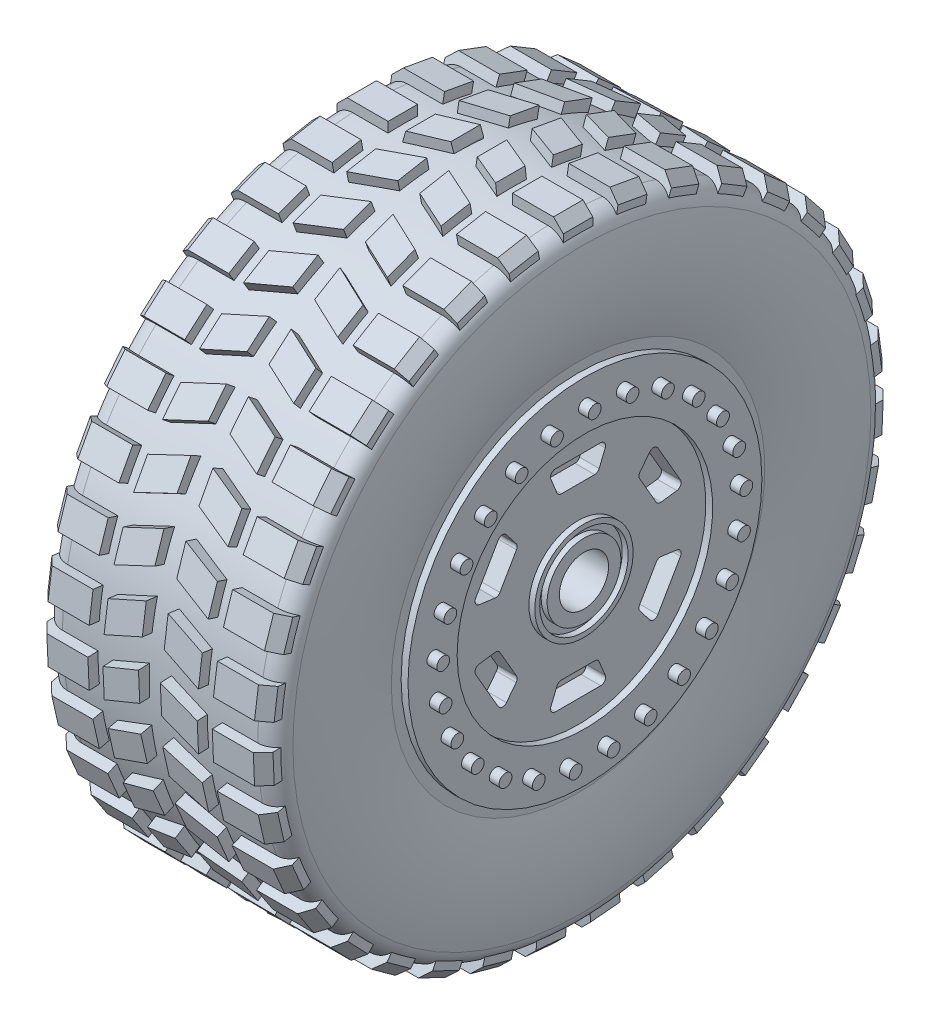
SolidWorks part; units mm, degrees
ref_plane "Front Plane" through (0, 0, 0) normal (0, 0, 1) x (1, 0, 0)
ref_plane "Top Plane" through (0, 0, 0) normal (0, 1, 0) x (1, 0, 0)
ref_plane "Right Plane" through (0, 0, 0) normal (1, 0, 0) x (0, 0, -1)
sketch "Sketch1" plane through (0, 0, 0) normal (0, 0, 1) x (1, 0, 0)
  line L0 (0, 0) -> (12.5125, 0) construction
  line L1 (0, 0) -> (0, 19)
  line L2 (0, 31) -> (11.5, 31)
  line L3 (11.5, 31) -> (11.5, 0)
  line L4 (11.5, 0) -> (0, 0)
  arc A0 (0, 19) -> (0, 31) centre (21.2241, 25) cw
  dimension "D1" = 19
  dimension "D2" = 31
  dimension "D3" = 11.5
revolve "Revolve1" add sketch "Sketch1" angle 360 about L0
sketch "Sketch2" plane through (0, 0, 0) normal (-1, 0, 0) x (0, 0, 1)
  circle A0 centre (0, 0) radius 18
  dimension "D1" = 36
extrude "Boss-Extrude1" add sketch "Sketch2" along normal blind 0.7
sketch "Sketch3" plane through (-0.7, 0, 0) normal (-1, 0, 0) x (0, 0, 1)
  circle A0 centre (0, 0) radius 13
  dimension "D1" = 26
extrude "Cut-Extrude1" cut sketch "Sketch3" against normal blind 0.7
sketch "Sketch4" plane through (0, 0, 0) normal (-1, 0, 0) x (0, 0, 1)
  line L0 (0, 0) -> (0, 8.2027) construction
  line L5 (1.6857, 8.2027) -> (-1.6857, 8.2027)
  line L6 (-2.1484, 8.5131) -> (-2.7624, 10.0114)
  line L7 (-2.2998, 10.701) -> (2.2998, 10.701)
  line L9 (2.1484, 8.5131) -> (2.7624, 10.0114)
  line L10 (0, 10.701) -> (0, 16.4054) construction
  line L11 (8.1174, 7.3422) -> (10.4172, 3.3588)
  line L12 (8.4467, 2.396) -> (10.0513, 2.6133)
  line L13 (7.9466, 2.6415) -> (6.2609, 5.5612)
  line L14 (6.2984, 6.1171) -> (7.2889, 7.398)
  line L15 (10.4172, -3.3588) -> (8.1174, -7.3422)
  line L16 (6.2984, -6.1171) -> (7.2889, -7.398)
  line L17 (6.2609, -5.5612) -> (7.9466, -2.6415)
  line L18 (8.4467, -2.396) -> (10.0513, -2.6133)
  line L19 (2.2998, -10.701) -> (-2.2998, -10.701)
  line L20 (-2.1484, -8.5131) -> (-2.7624, -10.0114)
  line L21 (-1.6857, -8.2027) -> (1.6857, -8.2027)
  line L22 (2.1484, -8.5131) -> (2.7624, -10.0114)
  line L23 (-8.1174, -7.3422) -> (-10.4172, -3.3588)
  line L24 (-8.4467, -2.396) -> (-10.0513, -2.6133)
  line L25 (-7.9466, -2.6415) -> (-6.2609, -5.5612)
  line L26 (-6.2984, -6.1171) -> (-7.2889, -7.398)
  line L27 (-10.4172, 3.3588) -> (-8.1174, 7.3422)
  line L28 (-6.2984, 6.1171) -> (-7.2889, 7.398)
  line L29 (-6.2609, 5.5612) -> (-7.9466, 2.6415)
  line L30 (-8.4467, 2.396) -> (-10.0513, 2.6133)
  arc A0 (2.7624, 10.0114) -> (2.2998, 10.701) centre (2.2998, 10.201) ccw
  arc A1 (2.1484, 8.5131) -> (1.6857, 8.2027) centre (1.6857, 8.7027) cw
  arc A2 (-1.6857, 8.2027) -> (-2.1484, 8.5131) centre (-1.6857, 8.7027) cw
  arc A3 (-2.7624, 10.0114) -> (-2.2998, 10.701) centre (-2.2998, 10.201) cw
  arc A4 (7.2889, 7.398) -> (8.1174, 7.3422) centre (7.6844, 7.0922) cw
  arc A5 (10.0513, 2.6133) -> (10.4172, 3.3588) centre (9.9842, 3.1088) ccw
  arc A6 (8.4467, 2.396) -> (7.9466, 2.6415) centre (8.3796, 2.8915) cw
  arc A7 (6.2609, 5.5612) -> (6.2984, 6.1171) centre (6.6939, 5.8112) cw
  arc A8 (10.0513, -2.6133) -> (10.4172, -3.3588) centre (9.9842, -3.1088) cw
  arc A9 (7.2889, -7.398) -> (8.1174, -7.3422) centre (7.6844, -7.0922) ccw
  arc A10 (6.2984, -6.1171) -> (6.2609, -5.5612) centre (6.6939, -5.8112) cw
  arc A11 (7.9466, -2.6415) -> (8.4467, -2.396) centre (8.3796, -2.8915) cw
  arc A12 (2.7624, -10.0114) -> (2.2998, -10.701) centre (2.2998, -10.201) cw
  arc A13 (-2.7624, -10.0114) -> (-2.2998, -10.701) centre (-2.2998, -10.201) ccw
  arc A14 (-2.1484, -8.5131) -> (-1.6857, -8.2027) centre (-1.6857, -8.7027) cw
  arc A15 (1.6857, -8.2027) -> (2.1484, -8.5131) centre (1.6857, -8.7027) cw
  arc A16 (-7.2889, -7.398) -> (-8.1174, -7.3422) centre (-7.6844, -7.0922) cw
  arc A17 (-10.0513, -2.6133) -> (-10.4172, -3.3588) centre (-9.9842, -3.1088) ccw
  arc A18 (-8.4467, -2.396) -> (-7.9466, -2.6415) centre (-8.3796, -2.8915) cw
  arc A19 (-6.2609, -5.5612) -> (-6.2984, -6.1171) centre (-6.6939, -5.8112) cw
  arc A20 (-10.0513, 2.6133) -> (-10.4172, 3.3588) centre (-9.9842, 3.1088) cw
  arc A21 (-7.2889, 7.398) -> (-8.1174, 7.3422) centre (-7.6844, 7.0922) ccw
  arc A22 (-6.2984, 6.1171) -> (-6.2609, 5.5612) centre (-6.6939, 5.8112) cw
  arc A23 (-7.9466, 2.6415) -> (-8.4467, 2.396) centre (-8.3796, 2.8915) cw
  point P12 (3.0451, 10.701)
  point P15 (2.0212, 8.2027)
  point P18 (-2.0212, 8.2027)
  point P21 (-3.0451, 10.701)
  point P83 (0, 0)
  dimension "D1" = 0.5
  dimension "D2" = 6
extrude "Cut-Extrude2" cut sketch "Sketch4" against normal blind 2
sketch "Sketch5" plane through (0, 0, 0) normal (-1, 0, 0) x (0, 0, 1)
  circle A0 centre (0, 0) radius 4.5
  circle A1 centre (0, 0) radius 5
  dimension "D1" = 10
  dimension "D2" = 9
extrude "Boss-Extrude2" add sketch "Sketch5" along normal blind 0.6
sketch "Sketch6" plane through (0, 0, 0) normal (-1, 0, 0) x (0, 0, 1)
  circle A0 centre (0, 0) radius 3.75
  dimension "D1" = 7.5
extrude "Boss-Extrude3" add sketch "Sketch6" along normal blind 0.6
sketch "Sketch7" plane through (-0.7, 0, 0) normal (-1, 0, 0) x (0, 0, 1)
  line L0 (0, 1.0659) -> (0, 26.7319) construction
  circle A0 centre (0, 15.4486) radius 0.65
  circle A1 centre (3.8419, 14.9633) radius 0.65
  circle A2 centre (7.4424, 13.5377) radius 0.65
  circle A3 centre (10.5753, 11.2615) radius 0.65
  circle A4 centre (13.0437, 8.2778) radius 0.65
  circle A5 centre (14.6925, 4.7739) radius 0.65
  circle A6 centre (15.4181, 0.97) radius 0.65
  circle A7 centre (15.175, -2.8948) radius 0.65
  circle A8 centre (13.9783, -6.5777) radius 0.65
  circle A9 centre (11.9034, -9.8473) radius 0.65
  circle A10 centre (9.0805, -12.4982) radius 0.65
  circle A11 centre (5.687, -14.3637) radius 0.65
  circle A12 centre (1.9362, -15.3268) radius 0.65
  circle A13 centre (-1.9362, -15.3268) radius 0.65
  circle A14 centre (-5.687, -14.3637) radius 0.65
  circle A15 centre (-9.0805, -12.4982) radius 0.65
  circle A16 centre (-11.9034, -9.8473) radius 0.65
  circle A17 centre (-13.9783, -6.5777) radius 0.65
  circle A18 centre (-15.175, -2.8948) radius 0.65
  circle A19 centre (-15.4181, 0.97) radius 0.65
  circle A20 centre (-14.6925, 4.7739) radius 0.65
  circle A21 centre (-13.0437, 8.2778) radius 0.65
  circle A22 centre (-10.5753, 11.2615) radius 0.65
  circle A23 centre (-7.4424, 13.5377) radius 0.65
  circle A24 centre (-3.8419, 14.9633) radius 0.65
  point P55 (0, 0)
  dimension "D1" = 1.3
  dimension "D2" = 25
extrude "Boss-Extrude4" add sketch "Sketch7" along normal blind 1
fillet "Fillet1" radius 2 1 edges at (0, 0, 31)
ref_plane "Plane1" through (0, 31, 0) normal (0, 1, 0) x (1, 0, 0)
sketch "Sketch8" plane through (0, 31, 0) normal (0, 1, 0) x (1, 0, 0)
  line L1 (0, -1.5) -> (5.1766, -1.5)
  line L2 (0, -1.5) -> (0, 1.5)
  line L3 (0, 1.5) -> (5.1766, 1.5)
  line L4 (5.1766, -1.5) -> (5.1766, 1.5)
  dimension "D1" = 1.5
  dimension "D2" = 3
extrude "Boss-Extrude5" add sketch "Sketch8" along normal blind 1 and the other way blind 1
chamfer "Chamfer1" distance 1 angle 45 1 edges at (0, 32, 0)
pattern_circular "CirPattern1" count 35 over 360 about axis through (0, 0, 0) along (1, 0, 0) of "Boss-Extrude5", "Chamfer1"
sketch "Sketch9" plane through (0, 31, 0) normal (0, 1, 0) x (1, 0, 0)
  line L0 (6.7047, -1.5491) -> (10.3876, 0)
  line L1 (10.3876, 0) -> (10.3876, 3)
  line L2 (10.3876, 3) -> (6.7047, 1.4509)
  line L3 (6.7047, 1.4509) -> (6.7047, -1.5491)
  dimension "D1" = 3
extrude "Boss-Extrude6" add sketch "Sketch9" along normal blind 1 and the other way blind 1
chamfer "Chamfer2" distance 1 angle 13 2 edges at (10.3876, 32, -1.5) (6.7047, 32, 0.0491)
pattern_circular "CirPattern2" count 35 over 360 about axis through (0, 0, 0) along (1, 0, 0) of "Boss-Extrude6"
mirror "Mirror1" about plane through (11.5, 31, 0) normal (-1, 0, 0) of bodies 111
sketch "Sketch10" plane through (23.6, 0, 0) normal (1, 0, 0) x (0, 0, -1)
  circle A0 centre (0, 0) radius 2.5
  dimension "D1" = 5
extrude "Cut-Extrude3" cut sketch "Sketch10" against normal blind 4
